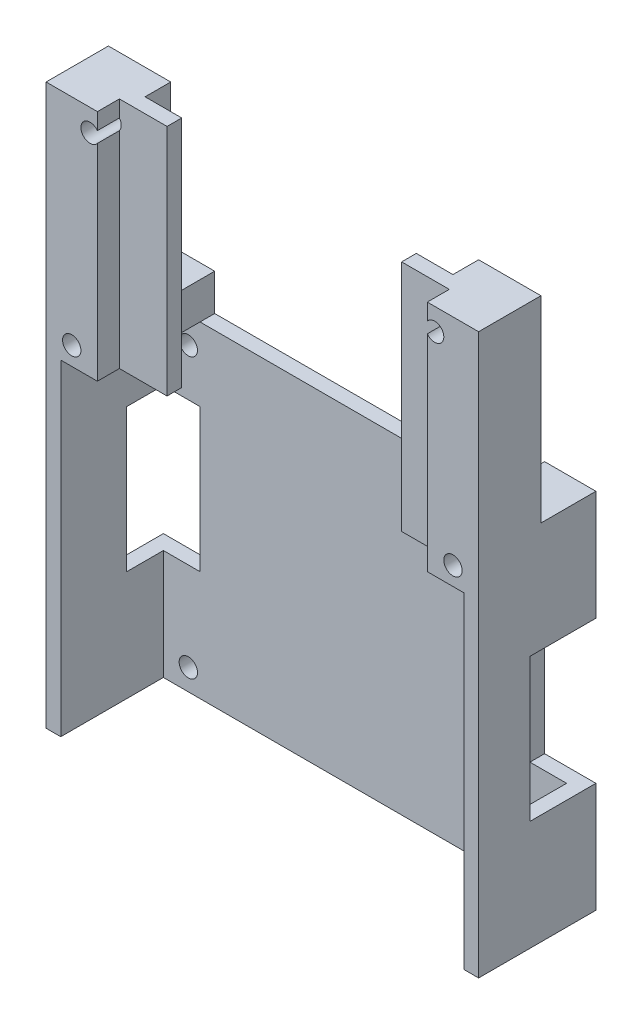
SolidWorks part; units mm, degrees
ref_plane "Front Plane" through (0, 0, 0) normal (0, 0, 1) x (1, 0, 0)
ref_plane "Top Plane" through (0, 0, 0) normal (0, 1, 0) x (1, 0, 0)
ref_plane "Right Plane" through (0, 0, 0) normal (1, 0, 0) x (0, 0, -1)
sketch "Sketch1" plane through (0, 0, 0) normal (0, 1, 0) x (1, 0, 0)
  line L0 (0, 0) -> (2, 0)
  line L1 (0, 0) -> (59, 0) construction
  line L2 (0, 0) -> (0, 9)
  line L3 (0, 9) -> (59, 9)
  line L4 (59, 0) -> (59, 9)
  line L5 (2, 0) -> (2, 7)
  line L6 (2, 7) -> (57, 7)
  line L7 (57, 7) -> (57, 0)
  line L8 (57, 0) -> (59, 0)
  dimension "D1" = 59
  dimension "D2" = 9
  dimension "D3" = 2
  dimension "D4" = 7
  dimension "D5" = 55
extrude "Boss-Extrude1" add sketch "Sketch1" along normal blind 44.5
sketch "Sketch3" plane through (0, 0, -9) normal (0, 0, -1) x (-1, 0, 0)
  line L0 (-59, 0) -> (-59, 8) construction
  line L1 (-59, 44.5) -> (-59, 0) construction
  line L2 (-59, 8) -> (-59, 2)
  line L3 (-59, 5) -> (-59.5, 5) construction
  line L4 (-59, 8) -> (-59.5, 8)
  line L5 (-59, 2) -> (-59.5, 2)
  line L6 (0, 0) -> (0, 8) construction
  line L7 (0, 44.5) -> (0, 0) construction
  line L8 (0, 8) -> (0.5, 8)
  line L9 (0, 8) -> (0, 2)
  line L10 (0, 2) -> (0.5, 2)
  line L11 (0, 5) -> (0.5, 5) construction
  arc A0 (-59.5, 8) -> (-59.5, 2) centre (-59.5, 5) ccw
  circle A1 centre (-59.5, 5) radius 1.25
  arc A2 (0.5, 8) -> (0.5, 2) centre (0.5, 5) cw
  circle A3 centre (0.5, 5) radius 1.25
  dimension "D4" = 3
  dimension "D5" = 2.5
  dimension "D11" = 3
  dimension "D12" = 2.5
  dimension "D1" = 8
  dimension "D2" = 6
  dimension "D3" = 0.5
  dimension "D6" = 8
  dimension "D7" = 0.5
  dimension "D8" = 6
  dimension "D9" = 0.5
sketch "Sketch4" plane through (0, 44.5, 0) normal (0, 1, 0) x (1, 0, 0)
  line L0 (59, 9) -> (0, 9) construction
  line L1 (0, 0) -> (7, 0)
  line L2 (0, 0) -> (0, 9)
  line L3 (0, 9) -> (7, 9)
  line L4 (7, 0) -> (7, 9)
  line L6 (59, 0) -> (52, 0)
  line L7 (59, 0) -> (59, 9)
  line L8 (59, 9) -> (52, 9)
  line L9 (52, 0) -> (52, 9)
  dimension "D1" = 7
  dimension "D2" = 7
extrude "Boss-Extrude3" add sketch "Sketch4" along normal blind 5
sketch "Sketch5" plane through (0, 0, -9) normal (0, 0, -1) x (-1, 0, 0)
  line L0 (-59, 49.5) -> (-52, 44.5) construction
  line L1 (0, 49.5) -> (-7, 44.5) construction
  circle A0 centre (-55.5, 47) radius 1.25
  circle A1 centre (-3.5, 47) radius 1.25
  dimension "D1" = 2.5
  dimension "D2" = 2.5
extrude "Cut-Extrude3" cut sketch "Sketch5" against normal through all
extrude "Boss-Extrude4" add sketch "Sketch3" against normal blind 3 contours L9 A3 | L2 A1 region at (58.6906, 5, -9) region at (0.3094, 5, -9)
mirror "Mirror2" about plane through (0, 0, 0) normal (0, 0, 1) of bodies 110
chamfer "Chamfer1" [suppressed] distance 4 angle 45
sketch "Sketch10" plane through (0, 0, -9) normal (0, 0, -1) x (-1, 0, 0)
  line L0 (-59, 49.5) -> (-59, 0) construction
  line L1 (-59, 15) -> (-52, 15)
  line L2 (-59, 15) -> (-59, 34.5)
  line L3 (-59, 34.5) -> (-52, 34.5)
  line L4 (-52, 15) -> (-52, 34.5)
  line L5 (-29.5, -2.6848) -> (-29.5, 49.4375) construction
  line L6 (-52, 44.5) -> (-7, 44.5) construction
  line L7 (-7, 15) -> (-7, 34.5)
  line L8 (0, 34.5) -> (-7, 34.5)
  line L9 (0, 15) -> (0, 34.5)
  line L10 (0, 15) -> (-7, 15)
  line L11 (-59, 49.5) -> (-52, 49.5) construction
  line L12 (-59, 0) -> (0, 0) construction
  point P10 (-29.5, 44.5)
  dimension "D1" = 15
  dimension "D2" = 15
  dimension "D3" = 7
extrude "Cut-Extrude6" cut sketch "Sketch10" against normal blind 7
chamfer "Chamfer3" distance 2 angle 45 2 edges at (0, 24.75, -2) (59, 24.75, -2)
sketch "Sketch9" plane through (0, 0, 0) normal (0, -1, 0) x (1, 0, 0)
  line L0 (59, 9) -> (59, -9) construction
  line L1 (0, 9) -> (59, 9)
  line L2 (0, 9) -> (0, 7)
  line L3 (0, 7) -> (59, 7)
  line L4 (59, 9) -> (59, 7)
  line L6 (2, 7) -> (57, 7) construction
extrude "Cut-Extrude5" cut sketch "Sketch9" against normal through all both and the other way through all
sketch "Sketch11" plane through (0, 0, -9) normal (0, 0, -1) x (-1, 0, 0)
  line L0 (-32.1436, 39.3669) -> (-24.5688, 39.3669)
  line L1 (-24.5688, 39.3669) -> (-28.2931, 29.3067)
  line L2 (-28.2931, 29.3067) -> (-20.7184, 29.3067)
  line L3 (-20.7184, 29.3067) -> (-37.5139, 7.1449)
  line L4 (-37.5139, 7.1449) -> (-33.0312, 22.2645)
  line L5 (-33.0312, 22.2645) -> (-40.606, 22.2645)
  line L6 (-40.606, 22.2645) -> (-32.1436, 39.3669)
extrude "Cut-Extrude7" cut sketch "Sketch11" against normal blind 0.5
sketch "Sketch12" plane through (0, 49.5, 0) normal (0, 1, 0) x (1, 0, 0)
  line L1 (0, -4) -> (13.5, -4)
  line L2 (0, -4) -> (0, -2)
  line L3 (0, -2) -> (13.5, -2)
  line L4 (13.5, -4) -> (13.5, -2)
  line L5 (59, -7) -> (59, 9) construction
  line L6 (45.5, -4) -> (59, -4)
  line L7 (45.5, -4) -> (45.5, -2)
  line L8 (45.5, -2) -> (59, -2)
  line L9 (59, -4) -> (59, -2)
  line L10 (7, -7) -> (7, 9) construction
  line L11 (29.5, 9) -> (29.5, -11.7033) construction
  line L12 (52, 9) -> (7, 9) construction
  line L14 (7, -7) -> (7, -2)
  line L15 (52, -7) -> (52, -2)
  line L16 (50.5, -2) -> (50.5, 1.5)
  line L17 (13.5, -2) -> (7, -2)
  line L21 (7, -2) -> (8.5, -2)
  line L22 (7, -2) -> (7, 1.5)
  line L23 (7, 1.5) -> (8.5, 1.5)
  line L24 (8.5, -2) -> (8.5, 1.5)
  line L25 (52, 1.5) -> (50.5, 1.5)
  line L26 (52, -2) -> (52, 1.5)
  line L27 (52, -2) -> (50.5, -2)
  line L28 (0, 9) -> (0, -7) construction
  line L29 (0, -2) -> (7, -2)
  line L30 (0, -2) -> (0, 1.5)
  line L31 (0, 1.5) -> (7, 1.5)
  line L32 (7, -2) -> (7, 1.5)
  line L33 (52, -2) -> (59, -2)
  line L34 (52, -2) -> (52, 1.5)
  line L35 (52, 1.5) -> (59, 1.5)
  line L36 (59, -2) -> (59, 1.5)
  line L38 (52, -7) -> (59, -7)
  line L39 (52, -7) -> (52, -4)
  line L40 (52, -4) -> (59, -4)
  line L41 (59, -7) -> (59, -4)
  line M9 (0, 9) -> (0, -7)
  line M10 (0, -7) -> (7, -7)
  line M11 (7, -7) -> (7, 9)
  dimension "D1" = 11
  dimension "D2" = 6.5
  dimension "D3" = 1.5
  dimension "D4" = 3.5
  dimension "D5" = 2
extrude "Boss-Extrude5" add sketch "Sketch12" along normal blind 26.85 contours L15 L6 L9 L8 | L1 L4 L3 M11 | L6 L15 L8 L7 | L3 L24 L23 M11 | L31 L3 M9 M11 | L8 L26 L25 L16 | L8 L36 L35 L26 | L3 L1 M9 M11 | L1 M9 M10 M11 | L38 L41 L6 L15 region at (3.5, 49.5, 3) region at (3.5, 49.5, 5.5) region at (10.25, 49.5, 3) region at (3.5, 49.5, 0.25) region at (7.75, 49.5, 0.25) region at (48.75, 49.5, 3) region at (55.5, 49.5, 3) region at (55.5, 49.5, 5.5) region at (55.5, 49.5, 0.25) region at (51.25, 49.5, 0.25)
sketch "Sketch7" plane through (0, 0, -9) normal (0, 0, -1) x (-1, 0, 0)
  line L0 (-59, 0) -> (-59, 2.9) construction
  line L1 (-59, 15) -> (-59, 0) construction
  line L2 (-59, 2.9) -> (0, 2.9) construction
  line L3 (0, 15) -> (0, 0) construction
  line L4 (-53.6, 2.9) -> (-5.4, 2.9)
  line L5 (-53.6, 2.9) -> (-53.6, 40.95) construction
  line L6 (-53.6, 40.95) -> (-5.4, 40.95) construction
  line L11 (-29.5, 93.7823) -> (-29.5, -12.7008) construction
  circle A0 centre (-53.6, 2.9) radius 1.25
  circle A1 centre (-5.4, 2.9) radius 1.25
  circle A2 centre (-53.6, 40.95) radius 1.25
  circle A3 centre (-5.4, 40.95) radius 1.25
  circle A4 centre (-6, 73.35) radius 1.25
  circle A5 centre (-53, 73.35) radius 1.25
  point P11 (-29.5, 2.9)
  dimension "D3" = 2.5
  dimension "D4" = 2.5
  dimension "D6" = 2.5
  dimension "D8" = 2.5
  dimension "D1" = 2.9
  dimension "D2" = 48.2
  dimension "D5" = 38.05
  dimension "D7" = 48.2
extrude "Cut-Extrude4" cut sketch "Sketch7" against normal through all contours A2 | A3 | A1 | A0 | A4 | A5 region at (5.4, 4.1146, -9) region at (54.8146, 2.9, -9) region at (53.6, 40.95, -9) region at (5.4, 40.95, -9) region at (6, 73.35, -9) region at (53, 73.35, -9)
extrude "Boss-Extrude6" add sketch "Sketch12<4>" against normal up to surface (5 mm away) contours L1 L4 L3 M11 | L6 L15 L8 L7 | L3 L24 L23 M11 | L8 L26 L25 L16 region at (10.25, 49.5, 3) region at (7.75, 49.5, 0.25) region at (48.75, 49.5, 3) region at (51.25, 49.5, 0.25) up to face at (29.5, 44.5, -8)
sketch "Sketch12<4>" plane through (0, 49.5, 0) normal (0, 1, 0) x (1, 0, 0) same geometry as "Sketch12"
